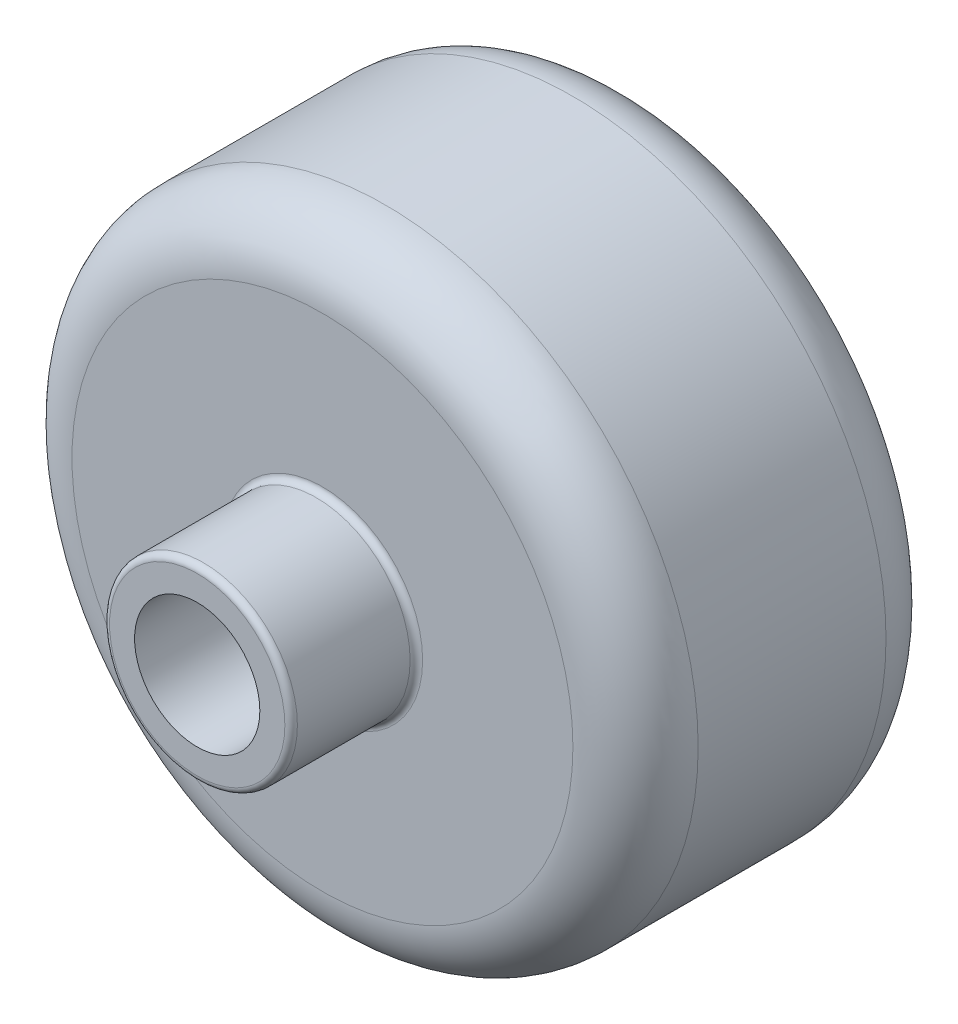
SolidWorks part; units mm, degrees
ref_plane "Plan de face" through (0, 0, 0) normal (0, 0, 1) x (1, 0, 0)
ref_plane "Plan de dessus" through (0, 0, 0) normal (0, 1, 0) x (1, 0, 0)
ref_plane "Plan de droite" through (0, 0, 0) normal (1, 0, 0) x (0, 0, -1)
sketch "Esquisse1" plane through (0, 0, 0) normal (0, 0, 1) x (1, 0, 0)
  circle A0 centre (0, 0) radius 5
  dimension "D1" = 10
extrude "Boss.-Extru.1" add sketch "Esquisse1" along normal blind 5
sketch "Esquisse2" plane through (0, 0, 5) normal (0, 0, 1) x (1, 0, 0)
  circle A0 centre (0, 0) radius 1.5
  dimension "D1" = 3
extrude "Boss.-Extru.2" add sketch "Esquisse2" along normal blind 2
sketch "Esquisse3" plane through (0, 0, 7) normal (0, 0, 1) x (1, 0, 0)
  circle A0 centre (0, 0) radius 1
  dimension "D1" = 2
extrude "Enlèv. mat.-Extru.1" cut sketch "Esquisse3" against normal through all
sketch "Esquisse4" plane through (0, 0, 0) normal (0, 0, -1) x (-1, 0, 0)
  circle A0 centre (0, 0) radius 2.5
  circle A1 centre (0, 0) radius 5
  circle A2 centre (0, 0) radius 5
  circle A3 centre (0, 0) radius 3
  circle A4 centre (0, 0) radius 4
  dimension "D2" = 5
  dimension "D1" = 0
  dimension "D3" = 2
  dimension "D4" = 1
extrude "Enlèv. mat.-Extru.2" cut sketch "Esquisse4" against normal blind 2 contours A4 A3 region at (3.8869, 0, 0)
fillet "Congé1" radius 1 2 edges at (-3, 0, 0) (5, 0, 0)
fillet "Congé2" radius 1 1 edges at (5, 0, 5)
fillet "Congé3" radius 0.1 2 edges at (1.5, 0, 7) (1.5, 0, 5)
